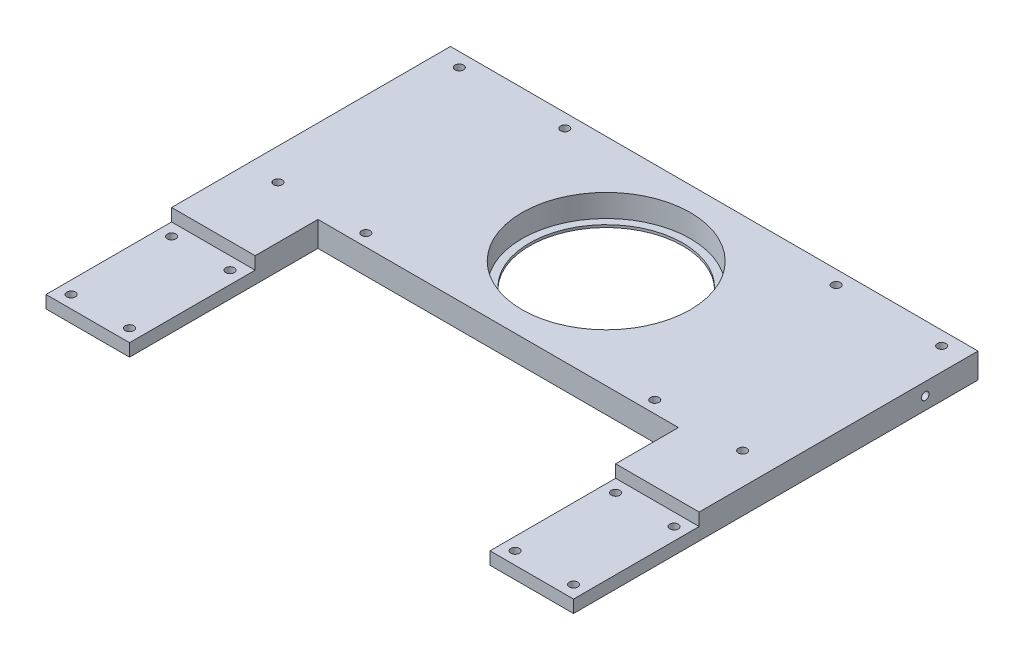
SolidWorks part; units mm, degrees
ref_plane "Ebene vorne" through (0, 0, 0) normal (0, 0, 1) x (1, 0, 0)
ref_plane "Ebene oben" through (0, 0, 0) normal (0, 1, 0) x (1, 0, 0)
ref_plane "Ebene rechts" through (0, 0, 0) normal (1, 0, 0) x (0, 0, -1)
sketch "Skizze1" plane through (0, 0, 0) normal (0, 1, 0) x (1, 0, 0)
  line L1 (-105, -200) -> (105, -200)
  line L2 (-105, -200) -> (-105, 200)
  line L3 (-105, 200) -> (105, 200)
  line L4 (105, -200) -> (105, 200)
  line L5 (-105, -200) -> (105, 200) construction
  line L6 (-105, 200) -> (105, -200) construction
  point P0 (0, 0)
  dimension "D1" = 210
  dimension "D2" = 400
extrude "Aufsatz-Linear austragen1" add sketch "Skizze1" along normal blind 10
ref_plane "Ebene1" through (0, -92.6125, 77.7111) normal (0, -0.766, 0.6428) x (1, 0, 0)
sketch "Skizze2" plane through (0, -92.6125, 77.7111) normal (0, -0.766, 0.6428) x (1, 0, 0)
  line L1 (-105, 159.6368) -> (105, 159.6368) construction
  circle A0 centre (0, 139.6368) radius 5
  dimension "D1" = 10
  dimension "D2" = 20
extrude "Schnitt-Linear austragen1" [suppressed] cut sketch "Skizze2" against normal blind 30 and the other way blind 10
sketch "Skizze3" [suppressed] plane through (0, -67.9923, 57.0523) normal (0, -0.766, 0.6428) x (1, 0, 0)
  circle A0 centre (0, 101.3345) radius 5
  dimension "D1" = 10
extrude "Aufsatz-Linear austragen2" [suppressed] add sketch "Skizze3" along normal blind 0.1
sketch "Skizze4" plane through (0, -92.6125, 77.7111) normal (0, -0.766, 0.6428) x (1, 0, 0)
  line L0 (0, 159.6368) -> (0, 159.9002) construction
  line L1 (-105, 159.6368) -> (105, 159.6368) construction
  line L2 (-25, 159.6368) -> (-25, 194.6368)
  line L3 (-25, 194.6368) -> (25, 194.6368)
  line L4 (-25, 159.6368) -> (25, 159.6368)
  line L5 (25, 159.6368) -> (25, 194.6368)
  point P10 (0, 194.6368)
  dimension "D1" = 50
  dimension "D2" = 35
extrude "Aufsatz-Linear austragen3" [suppressed] add sketch "Skizze4" against normal blind 10 separate body
sketch "Skizze5" plane through (0, 10, 0) normal (0, 1, 0) x (1, 0, 0)
  line L0 (0, 0) -> (0, -200) construction
  line L1 (-105, -200) -> (105, -200) construction
  line L2 (105, -200) -> (18, -200)
  line L3 (-18, -200) -> (-105, -46)
  line L4 (-105, 200) -> (-105, -200) construction
  line L5 (-105, -46) -> (-105, -200)
  line L6 (-105, -200) -> (-18, -200)
  line L7 (105, -46) -> (105, -200)
  line L8 (18, -200) -> (105, -46)
  line L9 (-105, 200) -> (-105, 115)
  line L10 (-105, 115) -> (105, 115)
  line L11 (105, -200) -> (105, 200) construction
  line L12 (105, 115) -> (105, 200)
  line L13 (105, 200) -> (-105, 200)
  line L14 (71.7468, -46) -> (-71.7468, -46)
  line L15 (-71.7468, -46) -> (-2.8247, -168)
  line L16 (71.7468, -46) -> (2.8247, -168)
  line L17 (-2.8247, -168) -> (2.8247, -168)
  line L18 (2.8247, -168) -> (0, -173) construction
  line L19 (-2.8247, -168) -> (0, -173) construction
  point P27 (0, -46)
  dimension "D1" = 36
  dimension "D2" = 154
  dimension "D3" = 85
  dimension "D4" = 32
  dimension "D5" = 27
extrude "Schnitt-Linear austragen2" cut sketch "Skizze5" against normal blind 10
sketch "Skizze6" plane through (0, 10, 0) normal (0, 1, 0) x (1, 0, 0)
  line L0 (0, -200) -> (0, -168) construction
  line L1 (-18, -200) -> (18, -200) construction
  line L2 (-2.8247, -168) -> (2.8247, -168) construction
  line L3 (0, -186.59) -> (-21.075, -186.59) construction
  circle A0 centre (-11, -195) radius 1.7
  circle A1 centre (-11, -178.18) radius 1.7
  circle A2 centre (11, -195) radius 1.7
  circle A3 centre (11, -178.18) radius 1.7
  dimension "D1" = 3.4
  dimension "D2" = 11
  dimension "D3" = 5
  dimension "D4" = 13.41
extrude "Schnitt-Linear austragen3" cut sketch "Skizze6" against normal through all
sketch "Skizze7" plane through (0, 0, 0) normal (0, -1, 0) x (1, 0, 0)
  line L0 (-11, 195) -> (-11, 200) construction
  line L1 (-18, 200) -> (18, 200) construction
  line L2 (-11, 195) -> (-5.1092, 195) construction
  line L3 (-11, 198.4064) -> (-8.05, 196.7032)
  line L4 (-8.05, 196.7032) -> (-8.05, 193.2968)
  line L5 (-11, 191.5936) -> (-8.05, 193.2968)
  line L6 (-11, 191.5936) -> (-13.95, 193.2968)
  line L7 (-13.95, 196.7032) -> (-13.95, 193.2968)
  line L8 (-11, 198.4064) -> (-13.95, 196.7032)
  line L9 (0, 200) -> (0, 121.6034) construction
  line L10 (11, 195) -> (11, 178.18) construction
  line L11 (11, 186.59) -> (0, 186.59) construction
  line L12 (11, 198.4064) -> (8.05, 196.7032)
  line L13 (11, 191.5936) -> (8.05, 193.2968)
  line L14 (8.05, 196.7032) -> (8.05, 193.2968)
  line L15 (11, 191.5936) -> (13.95, 193.2968)
  line L16 (13.95, 196.7032) -> (13.95, 193.2968)
  line L17 (11, 198.4064) -> (13.95, 196.7032)
  line L18 (-8.05, 176.4768) -> (-8.05, 179.8832)
  line L19 (-11, 181.5864) -> (-13.95, 179.8832)
  line L20 (-11, 181.5864) -> (-8.05, 179.8832)
  line L21 (-13.95, 176.4768) -> (-13.95, 179.8832)
  line L22 (-11, 174.7736) -> (-13.95, 176.4768)
  line L23 (-11, 174.7736) -> (-8.05, 176.4768)
  line L24 (8.05, 176.4768) -> (8.05, 179.8832)
  line L25 (11, 181.5864) -> (8.05, 179.8832)
  line L26 (11, 181.5864) -> (13.95, 179.8832)
  line L27 (13.95, 176.4768) -> (13.95, 179.8832)
  line L28 (11, 174.7736) -> (13.95, 176.4768)
  line L29 (11, 174.7736) -> (8.05, 176.4768)
  point P10 (-8.05, 195)
  dimension "D1" = 120
  dimension "D2" = 5.9
extrude "Schnitt-Linear austragen4" cut sketch "Skizze7" against normal blind 4
sketch "Skizze8" plane through (0, 10, 0) normal (0, 1, 0) x (1, 0, 0)
  line L0 (105, 105.41) -> (78.872, 105.41) construction
  line L1 (105, -46) -> (105, 115) construction
  line L2 (-105, 115) -> (105, 115) construction
  dimension "D1" = 9.59
ref_plane "Ebene2" through (0, 57.7725, -48.4769) normal (0, 0.766, -0.6428) x (-1, 0, 0)
sketch "Skizze9" plane through (0, 57.7725, -48.4769) normal (0, 0.766, -0.6428) x (-1, 0, 0)
  line L0 (-105, -74.3209) -> (-78.872, -74.3209) construction
  line L1 (-105, 41.6659) -> (-105, -81.6672) construction
  line L2 (0, -45.2589) -> (0, -16.2619) construction
  circle A0 centre (-100, -74.3209) radius 1.7
  circle A1 centre (100, -74.3209) radius 1.7
  circle A2 centre (-30, -74.3209) radius 1.7
  circle A3 centre (30, -74.3209) radius 1.7
  dimension "D1" = 3.4
  dimension "D2" = 5
  dimension "D3" = 30
extrude "Schnitt-Linear austragen5" [suppressed] cut sketch "Skizze9" against normal through all and the other way through all
ref_plane "Ebene3" through (0, 50.1121, -42.049) normal (0, 0.766, -0.6428) x (-1, 0, 0)
sketch "Skizze10" [suppressed] plane through (0, 55.0361, -46.1808) normal (0, 0.766, -0.6428) x (-1, 0, 0)
  line L0 (-95, -81.9813) -> (-100, -81.9813) construction
  line L1 (-95, -81.9813) -> (-95, -30.0694) construction
  line L2 (-95, -78.7482) -> (-97.8, -80.3647)
  line L3 (-97.8, -80.3647) -> (-97.8, -83.5979)
  line L4 (-95, -85.2145) -> (-97.8, -83.5979)
  line L5 (-95, -85.2145) -> (-92.2, -83.5979)
  line L6 (-92.2, -80.3647) -> (-92.2, -83.5979)
  line L7 (-95, -78.7482) -> (-92.2, -80.3647)
  line L8 (0, 0) -> (0, -45.6283) construction
  line L9 (-30, -81.9813) -> (-95, -81.9813) construction
  line L10 (-62.5, -81.9813) -> (-62.5, -23.1343) construction
  line L11 (-32.8, -80.3647) -> (-32.8, -83.5979)
  line L12 (-30, -85.2145) -> (-32.8, -83.5979)
  line L13 (-30, -85.2145) -> (-27.2, -83.5979)
  line L14 (-27.2, -80.3647) -> (-27.2, -83.5979)
  line L15 (-30, -78.7482) -> (-27.2, -80.3647)
  line L16 (-30, -78.7482) -> (-32.8, -80.3647)
  line L17 (95, -78.7482) -> (92.2, -80.3647)
  line L18 (92.2, -80.3647) -> (92.2, -83.5979)
  line L19 (95, -85.2145) -> (92.2, -83.5979)
  line L20 (95, -85.2145) -> (97.8, -83.5979)
  line L21 (97.8, -80.3647) -> (97.8, -83.5979)
  line L22 (95, -78.7482) -> (97.8, -80.3647)
  line L23 (30, -78.7482) -> (32.8, -80.3647)
  line L24 (30, -78.7482) -> (27.2, -80.3647)
  line L25 (27.2, -80.3647) -> (27.2, -83.5979)
  line L26 (30, -85.2145) -> (27.2, -83.5979)
  line L27 (30, -85.2145) -> (32.8, -83.5979)
  line L28 (32.8, -80.3647) -> (32.8, -83.5979)
  point P9 (-97.8, -81.9813)
  point P31 (97.8, -81.9813)
  dimension "D1" = 120
  dimension "D2" = 5.6
extrude "Schnitt-Linear austragen6" [suppressed] cut sketch "Skizze10" against normal blind 10 and the other way blind 5
sketch "Skizze13" plane through (0, 10, 0) normal (0, 1, 0) x (1, 0, 0)
  line L0 (71.7468, -46) -> (105, -46) construction
  line L1 (71.7468, -46) -> (96.9548, -60.2409) construction
  line L2 (105, -46) -> (18, -200) construction
  line L3 (0, 0) -> (0, -38.1435) construction
  line L4 (2.8247, -168) -> (71.7468, -46) construction
  line L5 (84.3508, -53.1205) -> (104.4794, -17.4905) construction
  line L6 (105, -46) -> (105, 115) construction
  line L7 (88.3734, -46) -> (88.3734, -1) construction
  line L8 (99, -48.9512) -> (101.4769, -44.5668) construction
  line L9 (87.7845, -76.4734) -> (62.5765, -62.2325) construction
  line L10 (77.1638, -70.4734) -> (91.1741, -70.4734) construction
  circle A0 centre (99, -48.9512) radius 1.7
  circle A1 centre (76.9708, -48.9512) radius 1.7
  circle A2 centre (86.8414, -70.4734) radius 1.7
  circle A3 centre (-86.8414, -70.4734) radius 1.7
  circle A4 centre (-99, -48.9512) radius 1.7
  circle A5 centre (-76.9708, -48.9512) radius 1.7
  dimension "D1" = 6
  dimension "D5" = 35
  dimension "D3" = 3.4
  dimension "D6" = 3.4
  dimension "D2" = 6
  dimension "D4" = 6
extrude "Schnitt-Linear austragen7" [suppressed] cut sketch "Skizze13" against normal through all
sketch "Skizze14" plane through (99.2964, 0, 56.096) normal (0.8707, 0, 0.4919) x (0.4919, 0, -0.8707)
  line L0 (-23.4043, 5) -> (-23.4043, 10)
  line L5 (11.5957, 0) -> (11.5957, 10) construction
  line L6 (-23.4043, 5) -> (11.5957, 5)
  line L7 (11.5957, 10) -> (-165.2799, 10) construction
  line L8 (-23.4043, 10) -> (11.5957, 10)
  line L9 (11.5957, 10) -> (11.5957, 5)
  dimension "D1" = 35
extrude "Schnitt-Linear austragen8" [suppressed] cut sketch "Skizze14" against normal up to surface (28.9525 mm away)
mirror "Spiegeln1" [suppressed] about plane through (0, 0, 0) normal (1, 0, 0)
sketch "Skizze15" [suppressed] plane through (95, 0, 0) normal (1, 0, 0) x (0, 0, -1)
  line L0 (4, 10) -> (4, 0)
  line L1 (4, 0) -> (65, 0)
  line L2 (65, 0) -> (65, 10)
  line L3 (65, 10) -> (4, 10)
extrude "Schnitt-Linear austragen9" [suppressed] cut sketch "Skizze15" against normal through all
sketch "Skizze16" plane through (0, 0, 0) normal (0, -1, 0) x (1, 0, 0)
  line L0 (0, 200) -> (0, 168) construction
  line L1 (-18, 200) -> (18, 200) construction
  line L2 (-2.8247, 168) -> (2.8247, 168) construction
  line L3 (11, 186.59) -> (0, 186.59) construction
  line L4 (11, 195) -> (11, 178.18) construction
  line L6 (-17.5, 183.09) -> (17.5, 183.09)
  line L7 (-17.5, 183.09) -> (-17.5, 190.09)
  line L8 (-17.5, 190.09) -> (17.5, 190.09)
  line L9 (17.5, 183.09) -> (17.5, 190.09)
  line L10 (-17.5, 183.09) -> (17.5, 190.09) construction
  line L11 (-17.5, 190.09) -> (17.5, 183.09) construction
  dimension "D1" = 7
  dimension "D2" = 35
extrude "Schnitt-Linear austragen10" cut sketch "Skizze16" against normal blind 5
sketch "Skizze17" plane through (17.5, 0, 0) normal (-1, 0, 0) x (0, 0, 1)
  line L0 (186.59, 0) -> (186.59, 11.1261) construction
  line L1 (183.09, 0) -> (190.09, 0) construction
  line L2 (183.09, 5) -> (186.59, 8.5)
  line L3 (186.59, 8.5) -> (190.09, 5)
  line L4 (190.09, 5) -> (183.09, 5)
  dimension "D1" = 90
extrude "Schnitt-Linear austragen11" cut sketch "Skizze17" along normal up to surface (35 mm away) up to face at (-17.5, 2.5, 186.59)
sketch "Skizze18" [suppressed] plane through (0, 10, 0) normal (0, 1, 0) x (1, 0, 0)
  line L0 (0, -210) -> (0, 0) construction
  line L1 (-18, -210) -> (18, -210) construction
  line L2 (62.5765, -72.2325) -> (35.4483, -67.5372)
  line L3 (15.3378, -155.8503) -> (-22.1774, -134.6566)
  line L4 (2.8247, -178) -> (62.5765, -72.2325) construction
  line L5 (-15.3378, -155.8503) -> (22.1774, -134.6566)
  line L6 (58.6594, -79.166) -> (40.7308, -76.063)
  line L7 (0, -147.1854) -> (19.5429, -147.1854) construction
  line L8 (0, -95.4) -> (31.4297, -95.4) construction
  line L9 (11.6488, -162.3803) -> (0, -155.7995)
  line L10 (-71.7468, -56) -> (-2.8247, -178) construction
  line L11 (0, -95.4) -> (-37.5153, -116.5937) construction
  line L12 (-37.5153, -116.5937) -> (-39.2566, -117.5774) construction
  line L13 (-11.6488, -162.3803) -> (0, -155.7995)
  line L14 (-58.6594, -79.166) -> (-40.7308, -76.063)
  line L15 (-62.5765, -72.2325) -> (-35.4483, -67.5372)
  circle A0 centre (0, -95.4) radius 33.5
  arc A1 (7.4594, -151.3994) -> (7.4594, -142.9713) centre (9.84, -147.1854) cw
  arc A2 (-7.4594, -151.3994) -> (-7.4594, -142.9713) centre (-9.84, -147.1854) ccw
  circle A3 centre (0, -95.4) radius 45.0879
  point P17 (0, -147.1854)
  point P36 (5, -147.1854)
  point P40 (-5, -147.1854)
  line M16 (62.5765, -72.2325) -> (2.8247, -178)
  line M18 (-2.8247, -178) -> (-71.7468, -56)
  dimension "D2" = 67
  dimension "D5" = 2
  dimension "D4" = 10
  dimension "D1" = 114.6
  dimension "D3" = 7.5
  dimension "D6" = 7.5
extrude "Aufsatz-Linear austragen4" [suppressed] add sketch "Skizze18" against normal blind 10 contours A3 L15 L14 M18 | A3 A0 M16 M18 | A3 L6 L2 M16 | A2 L5 L3 | A3 L3 L5 | L3 A1 L5 | L13 L9 L3 L5 M18 M16
sketch "Skizze19" [suppressed] plane through (0, 0, 0) normal (0, -1, 0) x (1, 0, 0)
  circle A0 centre (0, 35.4) radius 31.5
  circle A1 centre (0, 35.4) radius 33.5
  circle A2 centre (0, 35.4) radius 33.5 construction
  dimension "D1" = 63
extrude "Aufsatz-Linear austragen5" [suppressed] add sketch "Skizze19" against normal blind 1
sketch "Skizze20" plane through (0, 10, 0) normal (0, 1, 0) x (1, 0, 0)
  line L0 (105, 109.52) -> (55.4083, 109.52) construction
  line L1 (105, -46) -> (105, 115) construction
  line L2 (-105, 115) -> (105, 115) construction
  line L3 (0, 115) -> (0, 96.9732) construction
  line L4 (105, 33.82) -> (35.5869, 33.82) construction
  circle A0 centre (96, 109.52) radius 1.7
  circle A1 centre (54, 109.52) radius 1.7
  circle A2 centre (-54, 109.52) radius 1.7
  circle A3 centre (-96, 109.52) radius 1.7
  circle A4 centre (92.5, 33.82) radius 1.7
  circle A5 centre (57.5, 33.82) radius 1.7
  circle A6 centre (-92.5, 33.82) radius 1.7
  circle A7 centre (-57.5, 33.82) radius 1.7
  dimension "D1" = 3.4
  dimension "D2" = 5.48
  dimension "D3" = 9
  dimension "D4" = 42
  dimension "D5" = 75.7
  dimension "D6" = 12.5
  dimension "D7" = 35
extrude "Schnitt-Linear austragen12" cut sketch "Skizze20" against normal through all
sketch "Skizze21" plane through (0, 10, 0) normal (0, 1, 0) x (1, 0, 0)
  line L0 (-71.7468, -46) -> (-71.7468, 29)
  line L1 (-71.7468, 29) -> (71.7468, 29)
  line L2 (71.7468, 29) -> (71.7468, -46)
  line L3 (71.7468, -46) -> (-71.7468, -46) construction
  line L4 (-71.7468, -46) -> (71.7468, -46)
  dimension "D1" = 75
extrude "Schnitt-Linear austragen13" cut sketch "Skizze21" against normal through all
sketch "Skizze22" plane through (0, 10, 0) normal (0, 1, 0) x (1, 0, 0)
  line L0 (-71.7468, -46) -> (-2.8247, -168)
  arc A0 (-71.7468, -46) -> (-2.8247, -168) centre (55.7113, -54.4627) ccw
  line M19 (-2.8247, -168) -> (-71.7468, -46)
extrude "Schnitt-Linear austragen14" cut sketch "Skizze22" against normal through all contours M19 region at (-44.6278, 10, 111.1478)
sketch "Skizze23" plane through (0, 10, 0) normal (0, 1, 0) x (1, 0, 0)
  line L0 (-18, -200) -> (-105, -46) construction
  line L1 (-105, -46) -> (-18, -200)
  arc A0 (-18, -200) -> (-105, -46) centre (108.9155, -26.7263) cw
  arc A2 (-71.7468, -46) -> (-2.8247, -168) centre (55.7113, -54.4627) ccw construction
  dimension "D1" = 60
extrude "Aufsatz-Linear austragen6" add sketch "Skizze23" against normal blind 10
mirror "Spiegeln2" about plane through (0, 0, 0) normal (1, 0, 0) of "Aufsatz-Linear austragen6", "Schnitt-Linear austragen14"
sketch "Skizze25" plane through (0, 10, 0) normal (0, 1, 0) x (1, 0, 0)
  line L0 (-105, -46) -> (-71.7468, -46) construction
  line L1 (-105, 4) -> (-105, -46) construction
  line L2 (-105, 4) -> (-71.7468, 4) construction
  line L3 (-71.7468, 29) -> (-71.7468, -46) construction
  line L4 (-88.3734, 4) -> (-88.3734, -46) construction
  line L5 (-105, -21) -> (-71.7468, -21) construction
  line L6 (-105, 115) -> (-105, -46) construction
  circle A0 centre (-100, -1) radius 1.7
  circle A1 centre (-76.7468, -1) radius 1.7
  circle A2 centre (-76.7468, -41) radius 1.7
  circle A3 centre (-100, -41) radius 1.7
  dimension "D2" = 3.4
  dimension "D1" = 50
  dimension "D3" = 5
  dimension "D4" = 5
extrude "Schnitt-Linear austragen15" cut sketch "Skizze25" against normal through all
sketch "Skizze26" plane through (-105, 0, 0) normal (-1, 0, 0) x (0, 0, 1)
  line L0 (-4, 5) -> (-4, 13.1015)
  line L1 (46, 0) -> (46, 10) construction
  line L2 (46, 5) -> (-4, 5)
  line L4 (-115, 0) -> (46, 0) construction
  line L5 (46, 5) -> (46, 0)
  line L6 (-4, 13.1015) -> (200.6846, 82.5463)
  line L7 (200.6846, 82.5463) -> (242.9972, -41.0376)
  line L8 (242.9972, -41.0376) -> (91.2415, -60.2848)
  line L9 (91.2415, -60.2848) -> (46, 0)
  dimension "D1" = 50
mirror "Spiegeln3" about plane through (0, 0, 0) normal (1, 0, 0) of "Schnitt-Linear austragen15"
extrude "Schnitt-Linear austragen16" cut sketch "Skizze26" against normal through all
sketch "Skizze27" plane through (0, 10, 0) normal (0, 1, 0) x (1, 0, 0)
  line L0 (0, 29) -> (0, 115) construction
  line L1 (71.7468, 29) -> (-71.7468, 29) construction
  line L2 (-105, 115) -> (105, 115) construction
  circle A0 centre (0, 72) radius 33.5
  dimension "D1" = 67
extrude "Schnitt-Linear austragen17" cut sketch "Skizze27" against normal through all
sketch "Skizze28" plane through (0, 0, 0) normal (0, -1, 0) x (1, 0, 0)
  circle A0 centre (0, -72) radius 30.5
  circle A1 centre (0, -72) radius 33.5 construction
  circle A2 centre (0, -72) radius 36.0063
  dimension "D1" = 3
extrude "Aufsatz-Linear austragen7" add sketch "Skizze28" against normal blind 1
sketch "Skizze29" plane through (-105, 0, 0) normal (-1, 0, 0) x (0, 0, 1)
  line L0 (-115, 5) -> (-93.4233, 5) construction
  line L1 (-115, 0) -> (-115, 10) construction
  circle A0 centre (-94, 5) radius 1.5
  dimension "D1" = 3
  dimension "D2" = 21
extrude "Schnitt-Linear austragen18" cut sketch "Skizze29" against normal blind 10
sketch "Skizze30" plane through (0, 0, -115) normal (0, 0, -1) x (-1, 0, 0)
  line L0 (105, 5) -> (60.2539, 5) construction
  line L1 (105, 0) -> (105, 10) construction
  circle A0 centre (100, 5) radius 1.5
  circle A1 centre (84, 5) radius 1.5
  dimension "D1" = 3
  dimension "D2" = 5
  dimension "D3" = 21
extrude "Schnitt-Linear austragen19" cut sketch "Skizze30" against normal blind 10
mirror "Spiegeln4" about plane through (0, 0, 0) normal (1, 0, 0) of "Schnitt-Linear austragen18", "Schnitt-Linear austragen19"
sketch "Skizze31" plane through (0, 0, 0) normal (0, -1, 0) x (1, 0, 0)
  line L0 (0, -115) -> (0, -73.0202) construction
  line L1 (-105, -115) -> (105, -115) construction
  circle A0 centre (-96, -109.52) radius 2.95
  circle A1 centre (-54, -109.52) radius 2.95
  circle A2 centre (-92.5, -33.82) radius 2.95
  circle A3 centre (-57.5, -33.82) radius 2.95
  circle A4 centre (57.5, -33.82) radius 2.95
  circle A5 centre (92.5, -33.82) radius 2.95
  circle A6 centre (54, -109.52) radius 2.95
  circle A7 centre (96, -109.52) radius 2.95
  dimension "D1" = 5.9
extrude "Schnitt-Linear austragen20" cut sketch "Skizze31" against normal blind 3.5
